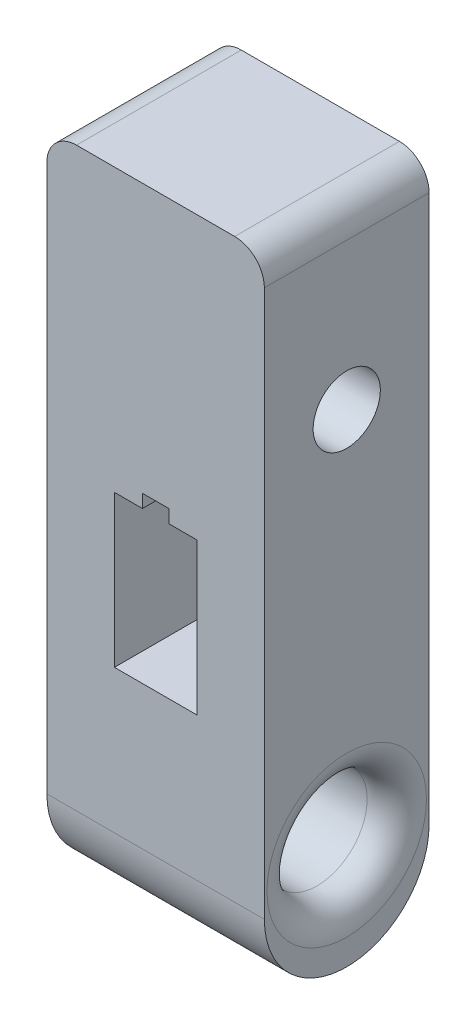
SolidWorks part; units mm, degrees
ref_plane "Front" through (0, 0, 0) normal (0, 0, 1) x (1, 0, 0)
ref_plane "Top" through (0, 0, 0) normal (0, 1, 0) x (1, 0, 0)
ref_plane "Right" through (0, 0, 0) normal (1, 0, 0) x (0, 0, -1)
sketch "Sketch1" plane through (0, 0, 0) normal (0, 0, 1) x (1, 0, 0)
  line L1 (-16.5, 50) -> (16.5, 50)
  line L2 (-16.5, 50) -> (-16.5, -50)
  line L3 (-16.5, -50) -> (16.5, -50)
  line L4 (16.5, 50) -> (16.5, -50)
  line L5 (-16.5, 50) -> (16.5, -50) construction
  line L6 (-16.5, -50) -> (16.5, 50) construction
  point P0 (0, 0)
  dimension "D1" = 33
  dimension "D2" = 100
extrude "Boss-Extrude1" add sketch "Sketch1" along normal blind 25
sketch "Sketch2" plane through (-16.5, 0, 0) normal (-1, 0, 0) x (0, 0, 1)
  line L0 (25, 50) -> (0, 50) construction
  circle A0 centre (12.5, 23.25) radius 5.1
  circle A1 centre (12.5, -34) radius 7.6
  dimension "D1" = 10.2
  dimension "D3" = 15.2
  dimension "D2" = 26.75
  dimension "D4" = 84
extrude "Cut-Extrude1" cut sketch "Sketch2" against normal through all
sketch "Sketch3" plane through (-16.5, 0, 0) normal (-1, 0, 0) x (0, 0, 1)
  circle A0 centre (12.5, 23.25) radius 11.1
  dimension "D1" = 22.2
extrude "Cut-Extrude2" cut sketch "Sketch3" against normal blind 3.5
sketch "Sketch4" plane through (-13, 0, 0) normal (-1, 0, 0) x (0, 0, 1)
  circle A0 centre (12.5, 31.25) radius 1.4
  circle A1 centre (12.5, 23.25) radius 5.1 construction
  circle A2 centre (12.5, 23.25) radius 5.1 construction
  circle A3 centre (20.5, 23.25) radius 1.4
  circle A4 centre (12.5, 15.25) radius 1.4
  circle A5 centre (4.5, 23.25) radius 1.4
  dimension "D1" = 2.8
  dimension "D2" = 8
  dimension "D3" = 4
extrude "Cut-Extrude3" cut sketch "Sketch4" against normal blind 10
fillet "Fillet1" radius 4.5 4 edges at (-16.5, -41.6, 12.5) (16.5, -41.6, 12.5) (16.5, 50, 12.5) (-16.5, 50, 12.5)
fillet "Fillet2" 2 edges at (0, -50, 0) (0, -50, 25) type full round first side face at (0, 15.4773, 0) second side face at (0, 15.4773, 25) middle face at (0, -50, 12.5)
sketch "Sketch5" plane through (0, 0, 0) normal (0, 0, -1) x (-1, 0, 0)
  line L1 (-6.25, 7.25) -> (6.25, 7.25)
  line L2 (-6.25, 7.25) -> (-6.25, -15.75)
  line L3 (-6.25, -15.75) -> (6.25, -15.75)
  line L4 (6.25, 7.25) -> (6.25, -15.75)
  line L5 (-6.25, 7.25) -> (6.25, -15.75) construction
  line L6 (-6.25, -15.75) -> (6.25, 7.25) construction
  line L7 (-12, 50) -> (12, 50) construction
  point P0 (0, -4.25)
  dimension "D1" = 12.5
  dimension "D2" = 23
  dimension "D3" = 54.25
extrude "Cut-Extrude4" cut sketch "Sketch5" against normal through all
sketch "Sketch6" plane through (0, 0, 0) normal (0, 0, -1) x (-1, 0, 0)
  line L9 (-6.25, 12) -> (6.25, 12)
  line L10 (-6.25, 12) -> (-6.25, -20.5)
  line L11 (-6.25, -20.5) -> (6.25, -20.5)
  line L12 (6.25, 12) -> (6.25, -20.5)
  line L13 (-6.25, 12) -> (6.25, -20.5) construction
  line L14 (-6.25, -20.5) -> (6.25, 12) construction
  point P0 (0, -4.25)
  point P1 (0, 0)
  point P6 (0, 0)
  dimension "D1" = 32.5
extrude "Cut-Extrude5" cut sketch "Sketch6" against normal blind 11
sketch "Sketch7" plane through (0, 0, 11) normal (0, 0, -1) x (-1, 0, 0)
  line L0 (6.25, -20.5) -> (6.25, 12) construction
  line L1 (-8.653, -4.25) -> (13.5219, -4.25) construction
  circle A0 centre (0, 9.5) radius 0.75
  circle A1 centre (0, -18) radius 0.75
  point P4 (6.25, -4.25)
  dimension "D1" = 13.75
  dimension "D2" = 1.5
extrude "Cut-Extrude6" cut sketch "Sketch7" against normal blind 7
sketch "Sketch8" plane through (0, 7.25, 0) normal (0, -1, 0) x (-1, 0, 0)
  line L5 (16.5, -25) -> (-16.5, -25) construction
  line L6 (2, -25) -> (-2, -25)
  line L7 (2, -25) -> (2, -21)
  line L8 (2, -21) -> (-2, -21)
  line L9 (-2, -25) -> (-2, -21)
  point P7 (0, -21)
  dimension "D1" = 21
  dimension "D2" = 4
extrude "Cut-Extrude7" cut sketch "Sketch8" against normal blind 2
ref_plane "Plane1" through (0, -25.5, 0) normal (0, 1, 0) x (1, 0, 0)
sketch "Sketch9" plane through (0, -25.5, 0) normal (0, 1, 0) x (1, 0, 0)
  line L1 (12, 0) -> (-12, 0) construction
  line L3 (12, 0) -> (13, 2)
  line L6 (0, 4.9362) -> (0, -9.9963) construction
  line L11 (13, 2) -> (9, 2)
  line L12 (11, 2) -> (11, -0.2343) construction
  line L13 (12, 0) -> (10, 0)
  line L14 (10, 0) -> (9, 2)
  line L15 (-12, 0) -> (-13, 2)
  line L16 (-13, 2) -> (-9, 2)
  line L17 (-10, 0) -> (-9, 2)
  line L18 (-12, 0) -> (-10, 0)
  point P7 (11, 0)
  dimension "D1" = 2
  dimension "D2" = 2
  dimension "D3" = 1
extrude "Boss-Extrude2" add sketch "Sketch9" along normal blind 42.5
sketch "Sketch10" plane through (0, -25.5, 0) normal (0, -1, 0) x (1, 0, 0)
  line L0 (16.5, 0) -> (-16.5, 0) construction
  line L1 (13, -2) -> (9, -2)
  line L2 (13, -2) -> (13, 0)
  line L3 (13, 0) -> (9, 0)
  line L4 (9, -2) -> (9, 0)
  line L5 (0, 5.6012) -> (0, -5.2676) construction
  line L6 (-13, 0) -> (-9, 0)
  line L7 (-9, -2) -> (-9, 0)
  line L8 (-13, -2) -> (-9, -2)
  line L9 (-13, -2) -> (-13, 0)
extrude "Boss-Extrude3" add sketch "Sketch10" against normal blind 2
